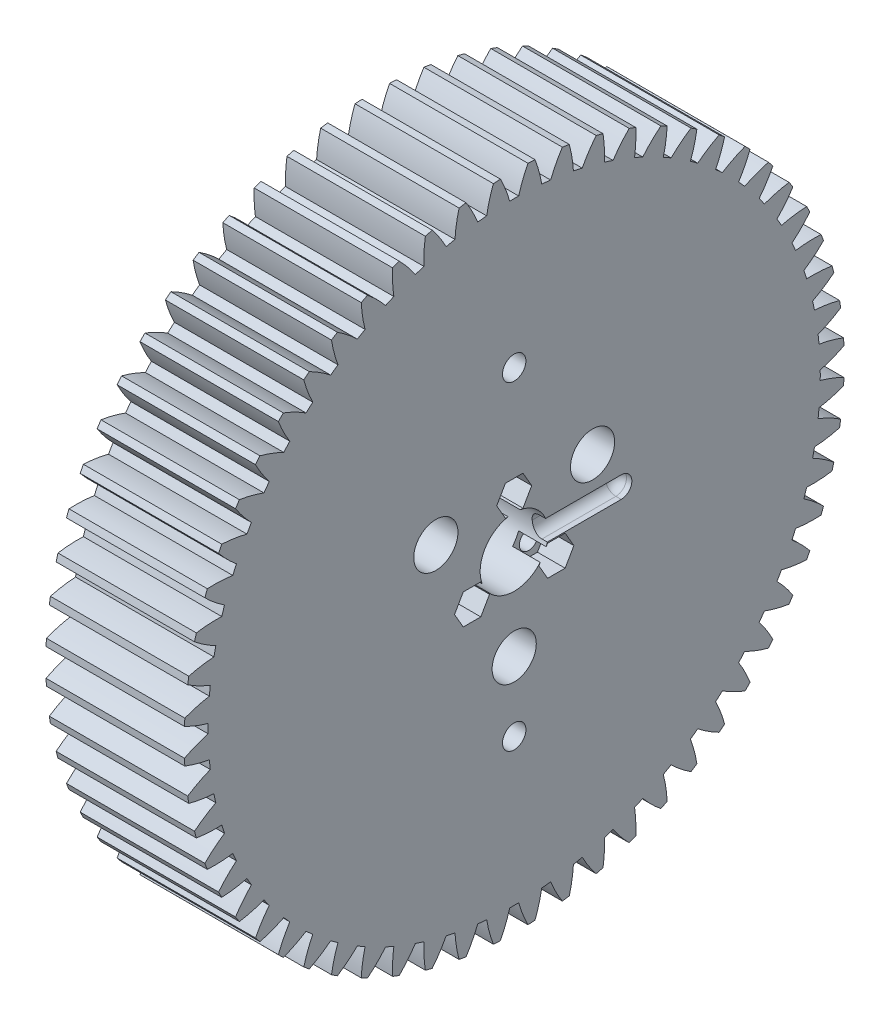
SolidWorks part; units mm, degrees
ref_plane "Plane1" through (0, 0, 0) normal (0, 0, 1) x (1, 0, 0)
ref_plane "Plane2" through (0, 0, 0) normal (0, 1, 0) x (1, 0, 0)
ref_plane "Plane3" through (0, 0, 0) normal (1, 0, 0) x (0, 0, -1)
other "Configuration Table"
sketch "HoldingSke" plane through (0, 0, 0) normal (0, 1, 0) x (1, 0, 0)
  line L0 (0, 0) -> (0.25, -0.433)
  line L1 (-15, 0) -> (100, 0) construction
  line L2 (0, 0) -> (-2.1039, 2.3779)
  line L3 (0, 0) -> (-11.863, 4.5341)
  line L4 (0, 0) -> (4.318, 7.479)
  line L5 (0, 0) -> (-46.8476, -17.4728)
  line L6 (0, 0) -> (-21.553, -14.5419)
  line L7 (-2.1039, 2.3779) -> (8.6586, 51.2059)
  line L8 (-76.2, 54.61) -> (-71.9, 54.61)
  line L9 (-71.009, 38.7566) -> (-53.1078, 45.2721)
  line L10 (-76.2, 71.12) -> (104.1128, 71.12)
  line L11 (0, 0) -> (-26, 0)
  line L12 (-76.2, 101.6) -> (-76.133, 101.6)
  line L13 (24.9733, 27.94) -> (52.9518, 28.4284)
  line L14 (24.9733, 27.94) -> (24.9743, 27.94)
  line L15 (24.9733, 27.94) -> (100.4006, 29.5858)
  line L16 (-63.627, -2) -> (-12.827, -2)
  circle A0 centre (0, 0) radius 25
  circle A1 centre (0, 0) radius 37.5
  circle A2 centre (0, 0) radius 37.5
  circle A3 centre (0, 0) radius 25
  dimension "Num_teeth" = 60
  dimension "Pitch_radius" = 180.3128
  dimension "Width" = 26
  dimension "Thickness" = 26
sketch "BasProSke" plane through (0, 0, 0) normal (0, 1, 0) x (1, 0, 0)
  line L0 (-10, 0) -> (60, 0) construction
  line L1 (0, 0) -> (0, 62)
  line L2 (0, 0) -> (26, 0)
  line L3 (26, 0) -> (26, 62)
  line L4 (26, 62) -> (0, 62)
  dimension "Thickness" = 26
  dimension "Diameter" = 124
revolve "Base-Revolve" add sketch "BasProSke" angle 360 about L0
sketch "TooCutSke" plane through (0, 0, 0) normal (1, 0, 0) x (0, 0, -1)
  line L1 (0, 0) -> (0, 107) construction
  line L2 (0, 0) -> (-1.6879, 59.9763) construction
  line L3 (0, 0) -> (-6.2785, 119.8004) construction
  line L4 (-1.6879, 59.9763) -> (-3.1392, 59.9002) construction
  arc A0 (0.8455, 57.4928) -> (-0.8455, 57.4928) centre (0, 0) ccw
  arc A1 (2.5963, 61.971) -> (-2.5963, 61.971) centre (0, 0) ccw
  circle A2 centre (0, 0) radius 60 construction
  circle A3 centre (0, 0) radius 56.3816 construction
  arc A4 (-0.8455, 57.4928) -> (-2.5963, 61.971) centre (-23.9609, 51.0368) ccw
  arc A5 (2.5963, 61.971) -> (0.8455, 57.4928) centre (23.9609, 51.0368) ccw
extrude "ToothCut" cut sketch "TooCutSke" along normal through all
fillet "Breaks" [suppressed] radius 0.04 tangent propagation no
fillet "RootFillets" [suppressed] radius 0.501
pattern_circular "TeethCuts" count 60 every 6 about axis through (-10, 0, 0) along (1, 0, 0) of "ToothCut", "RootFillets", "Breaks"
sketch "HubNeaOneSke" plane through (0, 0, 0) normal (-1, 0, 0) x (0, 0, 1)
  circle A0 centre (0, 0) radius 37.5
  dimension "Diameter" = 75
extrude "HubNearOne" [suppressed] add sketch "HubNeaOneSke" along normal blind 24.0001
sketch "HubNeaBotSke" plane through (0, 0, 0) normal (-1, 0, 0) x (0, 0, 1)
  circle A0 centre (0, 0) radius 37.5
  dimension "Diameter" = 75
extrude "HubNearBoth" [suppressed] add sketch "HubNeaBotSke" along normal blind 12
ref_plane "FarPln" through (26, 0, 0) normal (1, 0, 0) x (0, 0, -1)
sketch "HubFarSke" plane through (26, 0, 0) normal (1, 0, 0) x (0, 0, -1)
  circle A0 centre (0, 0) radius 37.5
  dimension "Diameter" = 75
extrude "HubFar" [suppressed] add sketch "HubFarSke" along normal blind 12
sketch "BorSke" plane through (0, 0, 0) normal (1, 0, 0) x (0, 0, -1)
  circle A0 centre (0, 0) radius 12.25
  dimension "Diameter" = 24.5
extrude "Bore" cut sketch "BorSke" along normal mid plane 100.0001
sketch "KeySke" plane through (0, 0, 0) normal (1, 0, 0) x (0, 0, -1)
  line L0 (-8, 0) -> (-8, 29.3)
  line L1 (-8, 29.3) -> (8, 29.3)
  line L2 (8, 29.3) -> (8, 0)
  line L3 (0, 0) -> (0, 34) construction
  line L4 (-8, 0) -> (8, 0)
  dimension "Width" = 16
extrude "Keyway" [suppressed] cut sketch "KeySke" along normal mid plane 100.0001
pattern_circular "Keyway2" [suppressed] count 2 every 90 about axis through (-10, 0, 0) along (1, 0, 0)
sketch "Sketch2" plane through (0, 0, 0) normal (-1, 0, 0) x (0, 0, 1)
  circle A0 centre (0, 0) radius 13.6
  dimension "D1" = 27.2
extrude "Cut-Extrude1" cut sketch "Sketch2" against normal blind 1.5
sketch "Sketch4" plane through (0, 0, 0) normal (-1, 0, 0) x (0, 0, 1)
  circle A0 centre (0, -17) radius 2.2
  circle A1 centre (0, 0) radius 12.25 construction
  circle A2 centre (-14.7224, 8.5) radius 2.2
  circle A3 centre (14.7224, 8.5) radius 2.2
  point P11 (0, 0)
  dimension "D1" = 4.4
  dimension "D2" = 17
  dimension "D3" = 3
extrude "Cut-Extrude2" cut sketch "Sketch4" against normal through all
sketch "Sketch7" plane through (26, 0, 0) normal (1, 0, 0) x (0, 0, -1)
  circle A0 centre (0, -17) radius 4.15
  circle A1 centre (-14.7224, 8.5) radius 4.15
  circle A2 centre (14.7224, 8.5) radius 4.15
  point P8 (0, 0)
  point P24 (0, 0)
  dimension "D1" = 8.3
extrude "Cut-Extrude3" cut sketch "Sketch7" against normal blind 17
sketch "Sketch8" plane through (0, 0, 0) normal (-1, 0, 0) x (0, 0, 1)
  circle A0 centre (0, -30) radius 2.2
  circle A1 centre (0, 0) radius 12.25 construction
  circle A2 centre (0, 30) radius 2.2
  dimension "D3" = 4.4
  dimension "D4" = 4.4
  dimension "D1" = 30
  dimension "D2" = 30
extrude "Cut-Extrude4" cut sketch "Sketch8" against normal through all
sketch "Sketch9" plane through (0, 0, 0) normal (-1, 0, 0) x (0, 0, 1)
  line L1 (4.2435, 30) -> (2.1218, 33.675)
  line L2 (2.1218, 33.675) -> (-2.1218, 33.675)
  line L3 (-2.1218, 33.675) -> (-4.2435, 30)
  line L4 (-4.2435, 30) -> (-2.1218, 26.325)
  line L5 (-2.1218, 26.325) -> (2.1218, 26.325)
  line L6 (2.1218, 26.325) -> (4.2435, 30)
  line L7 (4.2435, -30) -> (2.1218, -26.325)
  line L8 (2.1218, -26.325) -> (-2.1218, -26.325)
  line L9 (-2.1218, -26.325) -> (-4.2435, -30)
  line L10 (-4.2435, -30) -> (-2.1218, -33.675)
  line L11 (-2.1218, -33.675) -> (2.1218, -33.675)
  line L12 (2.1218, -33.675) -> (4.2435, -30)
  circle A2 centre (0, 30) radius 3.675 construction
  circle A3 centre (0, -30) radius 3.675 construction
  dimension "D1" = 7.35
  dimension "D2" = 7.35
extrude "Cut-Extrude5" cut sketch "Sketch9" against normal blind 8.3
sketch "Sketch11" plane through (26, 0, 0) normal (1, 0, 0) x (0, 0, -1)
  circle A0 centre (0, 0) radius 12.25
  circle A1 centre (0, 0) radius 6.4
  dimension "D1" = 12.8
extrude "Boss-Extrude2" add sketch "Sketch11" against normal blind 16
sketch "Sketch12" plane through (10, 0, 0) normal (-1, 0, 0) x (0, 0, 1)
  circle A0 centre (0, 9.1483) radius 1.75
  circle A1 centre (7.9227, -4.5741) radius 1.75
  circle A2 centre (-7.9227, -4.5741) radius 1.75
  point P8 (0, 0)
  dimension "D1" = 3.5
  dimension "D2" = 3
extrude "Cut-Extrude7" cut sketch "Sketch12" against normal blind 16
sketch "Sketch13" plane through (26, 0, 0) normal (1, 0, 0) x (0, 0, -1)
  line L0 (6.2772, -7.4241) -> (9.5681, -7.4241)
  line L1 (3.2909, 9.1483) -> (1.6454, 11.9983)
  line L2 (1.6454, 11.9983) -> (-1.6454, 11.9983)
  line L3 (-1.6454, 11.9983) -> (-3.2909, 9.1483)
  line L4 (-3.2909, 9.1483) -> (-1.6454, 6.2983)
  line L5 (-1.6454, 6.2983) -> (1.6454, 6.2983)
  line L6 (1.6454, 6.2983) -> (3.2909, 9.1483)
  line L7 (9.5681, -7.4241) -> (11.2136, -4.5741)
  line L8 (11.2136, -4.5741) -> (9.5681, -1.7241)
  line L9 (9.5681, -1.7241) -> (6.2772, -1.7241)
  line L10 (6.2772, -1.7241) -> (4.6318, -4.5741)
  line L11 (4.6318, -4.5741) -> (6.2772, -7.4241)
  line L12 (-9.5681, -1.7241) -> (-11.2136, -4.5741)
  line L13 (-11.2136, -4.5741) -> (-9.5681, -7.4241)
  line L14 (-9.5681, -7.4241) -> (-6.2772, -7.4241)
  line L15 (-6.2772, -7.4241) -> (-4.6318, -4.5741)
  line L16 (-4.6318, -4.5741) -> (-6.2772, -1.7241)
  line L17 (-6.2772, -1.7241) -> (-9.5681, -1.7241)
  circle A0 centre (0, 9.1483) radius 2.85 construction
  point P23 (0, 0)
  dimension "D1" = 5.7
extrude "Cut-Extrude8" cut sketch "Sketch13" against normal blind 5.2
sketch "Sketch14" plane through (26, 0, 0) normal (1, 0, 0) x (0, 0, -1)
  line L0 (0.1018, -1.503) -> (20.1018, -1.503)
  line L2 (20.1018, 2.497) -> (0.1018, 2.497)
  line L3 (0.1018, 2.497) -> (0.1018, -1.503)
  arc A0 (20.1018, 2.497) -> (20.1018, -1.503) centre (20.1018, 0.497) cw
  dimension "D1" = 4
  dimension "D2" = 20
extrude "Cut-Extrude9" cut sketch "Sketch14" against normal blind 3
fillet "Fillet1" radius 2 3 edges at (23, -1.503, -13.1614) (23, 0.497, -22.1018) (23, 2.497, -12.9973)
sketch "Sketch15" plane through (1.5, 0, 0) normal (-1, 0, 0) x (0, 0, 1)
  circle A0 centre (0, 0) radius 13.6
  circle A1 centre (0, 0) radius 12.25
extrude "Boss-Extrude3" add sketch "Sketch15" along normal blind 1.5
sketch "Sketch16" plane through (0, 0, 0) normal (-1, 0, 0) x (0, 0, 1)
  circle A0 centre (0, 0) radius 12.25
  circle A1 centre (0, 0) radius 23
  dimension "D1" = 46
extrude "Boss-Extrude4" add sketch "Sketch16" along normal blind 7.5
sketch "Sketch17" plane through (0, 0, 0) normal (1, 0, 0) x (0, 0, -1)
  circle A0 centre (0, -17) radius 2.2
  circle A1 centre (14.7224, 8.5) radius 2.2
  circle A2 centre (-14.7224, 8.5) radius 2.2
  dimension "D1" = 4.4
  dimension "D2" = 4.4
  dimension "D3" = 4.4
extrude "Cut-Extrude10" cut sketch "Sketch17" against normal through all
sketch "Sketch18" plane through (-7.5, 0, 0) normal (-1, 0, 0) x (0, 0, 1)
  circle A0 centre (0, 0) radius 13.6
  dimension "D1" = 27.2
extrude "Cut-Extrude11" cut sketch "Sketch18" against normal blind 1.5
equation "' \"Module@HoldingSke\" = 6.35"
equation "' \"Num_teeth@HoldingSke\" = 12"
equation "' \"Ap@HoldingSke\" =  20"
equation "' \"Ap@HoldingSke\" = 20"
equation "' \"Width@HoldingSke\" = 0.5 * 25.4"
equation "' \"Hub_dia@HoldingSke\"= 1 * 25.4"
equation "' \"Hub_dia@HoldingSke\" = 1 * 25.4"
equation "' \"Overall_len@HoldingSke\" = 1.0 * 25.4"
equation "' \"Bore@HoldingSke\" = 0.75 * 25.4"
equation "' \"T_dim@HoldingSke\" = 0.1 * 25.4"
equation "' \"Width@KeySke\" = 0.25 * 25.4"
equation "' \"Show_teeth@HoldingSke\" = 13"
equation "' \"Backlash@HoldingSke\" = 0.009 * 25.4"
equation "' \"Addendum_fac@HoldingSke\" = 1.0"
equation "' \"Dedendum_fac@HoldingSke\" = 1.25"
equation "' \"Dedendum_add@HoldingSke\" = 0.00005 * 25.4"
equation "' \"Clearance_fac@HoldingSke\" = 0.25"
equation "\"Pitch@HoldingSke\" = 1 / \"Module@HoldingSke\""
equation "\"Overcut_dia@TooCutSke\" = (\"Num_teeth@HoldingSke\" + 2 * \"Addendum_fac@HoldingSke\") / \"Pitch@HoldingSke\" + 0.002 * 25.4"
equation "\"Pitch_dia@TooCutSke\" = \"Num_teeth@HoldingSke\" / \"Pitch@HoldingSke\""
equation "\"Base_dia@TooCutSke\" = \"Num_teeth@HoldingSke\" / \"Pitch@HoldingSke\" * cos((\"Ap@HoldingSke\"  * 3.14159265 / 180))"
equation "\"Root_dia@TooCutSke\" = (\"Num_teeth@HoldingSke\" + 2) / \"Pitch@HoldingSke\" - 2 * (\"Addendum_fac@HoldingSke\" + \"Dedendum_fac@HoldingSke\") / \"Pitch@HoldingSke\" - \"Dedendum_add@HoldingSke\" * 2"
equation "\"Half_ang@TooCutSke\" = 180 / \"Num_teeth@HoldingSke\""
equation "\"Half_CT@TooCutSke\" = \"Num_teeth@HoldingSke\" / \"Pitch@HoldingSke\" * sin((3.14159265 / 2 / \"Num_teeth@HoldingSke\")) / 2 - 7 * \"Backlash@HoldingSke\" / 4"
equation "\"Flank_rad@TooCutSke\" = \"Num_teeth@HoldingSke\" / \"Pitch@HoldingSke\" / 5"
equation "\"Radius@RootFillets\" = \"Clearance_fac@HoldingSke\" / \"Pitch@HoldingSke\" + \"Dedendum_add@HoldingSke\""
equation "\"Break_rad@Breaks\" = 0.02 / \"Pitch@HoldingSke\""
equation "\"Thickness@HoldingSke\" = \"Width@HoldingSke\""
equation "\"OAL@HoldingSke\" = \"Thickness@HoldingSke\""
equation "\"MHD@HoldingSke\" = (\"Num_teeth@HoldingSke\" + 2) / \"Pitch@HoldingSke\" - 2 * (\"Addendum_fac@HoldingSke\" + \"Dedendum_fac@HoldingSke\")  / \"Pitch@HoldingSke\" - \"Dedendum_add@HoldingSke\" * 2"
equation "\"MBD@HoldingSke\" = (\"Num_teeth@HoldingSke\" + 2) / \"Pitch@HoldingSke\" - 2 * (\"Addendum_fac@HoldingSke\" + \"Dedendum_fac@HoldingSke\")  / \"Pitch@HoldingSke\" - \"Dedendum_add@HoldingSke\" * 2 - 0.002 * 25.4"
equation "\"MHD@HoldingSke\" = ((sgn( \"MHD@HoldingSke\" - \"Hub_dia@HoldingSke\" )-1)*( \"MHD@HoldingSke\" - \"Hub_dia@HoldingSke\" ))/-2+ \"Hub_dia@HoldingSke\""
equation "\"MBD@HoldingSke\" = ((sgn( \"MBD@HoldingSke\" - \"Bore@HoldingSke\" )-1)*( \"MBD@HoldingSke\" - \"Bore@HoldingSke\" ))/-2+ \"Bore@HoldingSke\""
equation "\"OAL@HoldingSke\" = ((sgn( \"OAL@HoldingSke\" - \"Overall_len@HoldingSke\" )+1)*( \"OAL@HoldingSke\" - \"Overall_len@HoldingSke\" ))/2 + \"Overall_len@HoldingSke\" + 0.000002 * 25.4"
equation "\"Num_teeth@TeethCuts\" = int( \"Show_teeth@HoldingSke\" ) + 1"
equation "\"Num_teeth@TeethCuts\" = ((sgn( \"Num_teeth@TeethCuts\" - \"Num_teeth@HoldingSke\" )-1)*( \"Num_teeth@TeethCuts\" - \"Num_teeth@HoldingSke\" ))/-2+ \"Num_teeth@HoldingSke\""
equation "\"Num_teeth@TeethCuts\" = ((sgn( \"Num_teeth@TeethCuts\" - 2.0)+1)*( \"Num_teeth@TeethCuts\" - 2.0))/2 +2.0"
equation "\"Angle@TeethCuts\" = 360.0 / \"Num_teeth@HoldingSke\""
equation "\"Diameter@BasProSke\" = (\"Num_teeth@HoldingSke\" + 2 * \"Addendum_fac@HoldingSke\") / \"Pitch@HoldingSke\""
equation "\"Thickness@BasProSke\"  = \"Thickness@HoldingSke\""
equation "' \"Fillet_rad@BasProSke\" =  \"Thickness@HoldingSke\" * 0.05"
equation "' \"Fillet_rad@BasProSke\" = \"Thickness@HoldingSke\" * 0.05"
equation "\"MHD@HoldingSke\" = ((sgn( \"MHD@HoldingSke\" - \"Root_dia@TooCutSke\" )-1)*( \"MHD@HoldingSke\" - \"Root_dia@TooCutSke\" ))/-2+ \"Root_dia@TooCutSke\""
equation "\"Diameter@HubNeaOneSke\" = \"MHD@HoldingSke\""
equation "\"Length@HubNearOne\" = \"OAL@HoldingSke\" - \"Thickness@BasProSke\""
equation "\"Diameter@HubNeaBotSke\" = \"MHD@HoldingSke\""
equation "\"Length@HubNearBoth\" = ( \"OAL@HoldingSke\" - \"Thickness@BasProSke\" ) / 2.0"
equation "\"Thickness@FarPln\" = \"Thickness@BasProSke\""
equation "\"Diameter@HubFarSke\" = \"MHD@HoldingSke\""
equation "\"Length@HubFar\" = ( \"OAL@HoldingSke\" - \"Thickness@BasProSke\" ) / 2.0"
equation "\"Diameter@BorSke\"=24.5"
equation "\"D1@Bore\" = \"OAL@HoldingSke\" * 2.0"
equation "\"D1@Keyway\" = \"OAL@HoldingSke\" * 2.0"
equation "\"Offset@KeySke\" = \"T_dim@HoldingSke\" + \"MBD@HoldingSke\" / 2.0"
equation "\"165.2.000mm\"=16"
